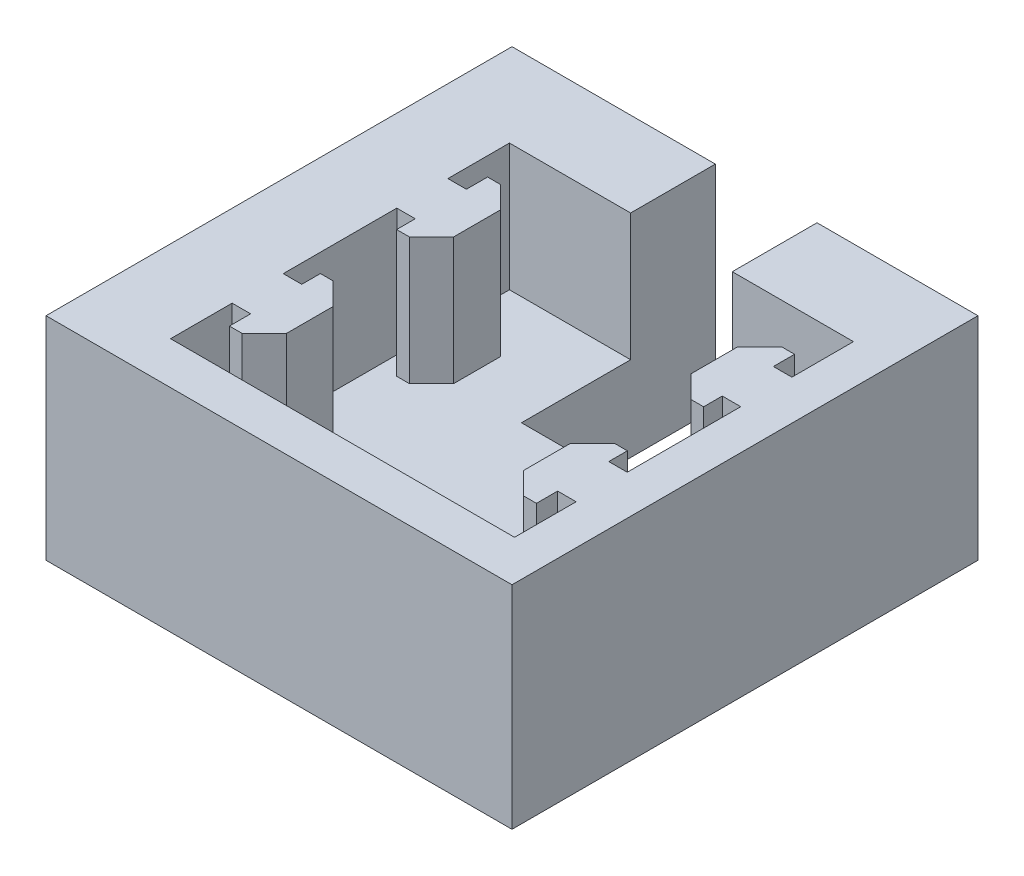
SolidWorks part; units mm, degrees
ref_plane "Front Plane" through (0, 0, 0) normal (0, 0, 1) x (1, 0, 0)
ref_plane "Top Plane" through (0, 0, 0) normal (0, 1, 0) x (1, 0, 0)
ref_plane "Right Plane" through (0, 0, 0) normal (1, 0, 0) x (0, 0, -1)
sketch "Sketch1" plane through (0, 0, 0) normal (0, 1, 0) x (1, 0, 0)
  line L1 (0, 0) -> (-55, 0)
  line L2 (0, 0) -> (0, -55)
  line L3 (0, -55) -> (-55, -55)
  line L4 (-55, 0) -> (-55, -55)
  dimension "D1" = 55
  dimension "D2" = 55
extrude "Boss-Extrude1" add sketch "Sketch1" along normal blind 10
sketch "Sketch2" plane through (0, 10, 0) normal (0, 1, 0) x (1, 0, 0)
  line L0 (-45.3163, -17.2674) -> (-43.1163, -17.2674)
  line L2 (-43.1163, -17.2674) -> (-43.1163, -14.7674)
  line L3 (-43.1163, -14.7674) -> (-41.6163, -14.7674)
  line L4 (-41.6163, -14.7674) -> (-39, -17.3837)
  line L5 (-39, -17.3837) -> (-39, -22.8837)
  line L6 (-39, -22.8837) -> (-41.6163, -25.5)
  line L7 (-41.6163, -25.5) -> (-43.1163, -25.5)
  line L8 (-43.1163, -25.5) -> (-43.1163, -23.3)
  line L9 (-43.1163, -23.3) -> (-45.3163, -23.3)
  line L10 (-45.3163, -23.3) -> (-45.3163, -17.2674)
  line L13 (-25, 0) -> (-25, -55) construction
  line L15 (-55, -30) -> (-3.9273, -30) construction
  line L18 (-6.8837, -23.3) -> (-4.6837, -23.3)
  line L19 (-6.8837, -25.5) -> (-6.8837, -23.3)
  line L20 (-8.3837, -25.5) -> (-6.8837, -25.5)
  line L21 (-11, -22.8837) -> (-8.3837, -25.5)
  line L22 (-11, -17.3837) -> (-11, -22.8837)
  line L23 (-8.3837, -14.7674) -> (-11, -17.3837)
  line L24 (-6.8837, -14.7674) -> (-8.3837, -14.7674)
  line L25 (-6.8837, -17.2674) -> (-6.8837, -14.7674)
  line L26 (-4.6837, -17.2674) -> (-6.8837, -17.2674)
  line L27 (-4.6837, -23.3) -> (-4.6837, -17.2674)
  line L28 (-43.1163, -36.7) -> (-45.3163, -36.7)
  line L29 (-43.1163, -34.5) -> (-43.1163, -36.7)
  line L30 (-41.6163, -34.5) -> (-43.1163, -34.5)
  line L31 (-39, -37.1163) -> (-41.6163, -34.5)
  line L32 (-39, -42.6163) -> (-39, -37.1163)
  line L33 (-41.6163, -45.2326) -> (-39, -42.6163)
  line L34 (-43.1163, -45.2326) -> (-41.6163, -45.2326)
  line L35 (-43.1163, -42.7326) -> (-43.1163, -45.2326)
  line L36 (-45.3163, -42.7326) -> (-43.1163, -42.7326)
  line L37 (-45.3163, -36.7) -> (-45.3163, -42.7326)
  line L38 (-6.8837, -34.5) -> (-6.8837, -36.7)
  line L39 (-8.3837, -34.5) -> (-6.8837, -34.5)
  line L40 (-11, -37.1163) -> (-8.3837, -34.5)
  line L41 (-11, -42.6163) -> (-11, -37.1163)
  line L42 (-8.3837, -45.2326) -> (-11, -42.6163)
  line L43 (-6.8837, -45.2326) -> (-8.3837, -45.2326)
  line L44 (-6.8837, -42.7326) -> (-6.8837, -45.2326)
  line L45 (-4.6837, -42.7326) -> (-6.8837, -42.7326)
  line L46 (-4.6837, -36.7) -> (-4.6837, -42.7326)
  line L47 (-6.8837, -36.7) -> (-4.6837, -36.7)
  line L48 (-55, -55) -> (0, -55) construction
  line L49 (-55, 0) -> (-55, -55) construction
  point P20 (-55, -27.5)
  point P52 (-27.5, -55)
  dimension "D1" = 2.2
  dimension "D2" = 2.2
  dimension "D3" = 2.5
  dimension "D4" = 2.2
  dimension "D5" = 3.7
  dimension "D6" = 3.7
  dimension "D7" = 5.5
  dimension "D8" = 1.5
  dimension "D9" = 1.5
  dimension "D10" = 4.5
  dimension "D11" = 14
  dimension "D12" = 0
  dimension "D13" = 2.5
  dimension "D14" = 2.5
  dimension "D15" = 0
extrude "Boss-Extrude3" add sketch "Sketch2" along normal blind 15
sketch "Sketch3" plane through (0, 10, 0) normal (0, 1, 0) x (1, 0, 0)
  line L0 (0, -55) -> (0, 0) construction
  line L1 (-55, 0) -> (0, 0)
  line L2 (-55, 0) -> (-55, -10)
  line L3 (-55, -10) -> (0, -10)
  line L4 (0, 0) -> (0, -10)
  line L6 (-55, -55) -> (0, -55)
  line L7 (-55, -55) -> (-55, -50)
  line L8 (-55, -50) -> (0, -50)
  line L9 (0, -55) -> (0, -50)
  line L10 (-55, -10) -> (-45.3, -10)
  line L11 (-55, -10) -> (-55, -50)
  line L12 (-55, -50) -> (-45.3, -50)
  line L13 (-45.3, -10) -> (-45.3, -50)
  line L14 (0, -10) -> (-4.7, -10)
  line L15 (0, -10) -> (0, -50)
  line L16 (0, -50) -> (-4.7, -50)
  line L17 (-4.7, -10) -> (-4.7, -50)
  line M15 (-45.3163, -42.7326) -> (-45.3163, -36.7)
  line M17 (-45.3163, -23.3) -> (-45.3163, -17.2674)
  line M27 (0, -55) -> (0, 0)
  line M28 (0, 0) -> (-55, 0)
  line M29 (-55, 0) -> (-55, -55)
  line M30 (-55, -55) -> (0, -55)
  line M39 (-4.6837, -17.2674) -> (-4.6837, -23.3)
  line M44 (-4.6837, -36.7) -> (-4.6837, -42.7326)
  dimension "D1" = 10
  dimension "D2" = 5
  dimension "D3" = 9.7
  dimension "D4" = 4.7
extrude "Boss-Extrude5" add sketch "Sketch3" along normal blind 15 contours L3 M29 M27 M28 | L13 L3 L8 M29 M15 M17 | L8 M29 M30 M27 | L3 L17 L8 M39 M44 M27 | L15 L14 L17 L16 | L2 L1 L4 L3 | L7 L6 L9 L8 | L11 L10 L13 L12 region at (-27.5, 10, 5) region at (-50.15, 10, 30) region at (-2.35, 10, 30) region at (-27.5, 10, 52.5)
sketch "Sketch7" plane through (0, 25, 0) normal (0, 1, 0) x (1, 0, 0)
  line L0 (-25, 0) -> (-25, -53.168) construction
  line L1 (-31, 0) -> (-19, 0)
  line L2 (-31, 0) -> (-31, -22.8837)
  line L3 (-31, -22.8837) -> (-19, -22.8837)
  line L4 (-19, 0) -> (-19, -22.8837)
  line L8 (0, 0) -> (-55, 0) construction
  point P8 (-27.5, 0)
  dimension "D1" = 12
  dimension "D2" = 6
  dimension "D3" = 0
  dimension "D4" = 0
  dimension "D5" = 2.5
  dimension "D6" = 0
extrude "Cut-Extrude3" cut sketch "Sketch7" against normal blind 45
